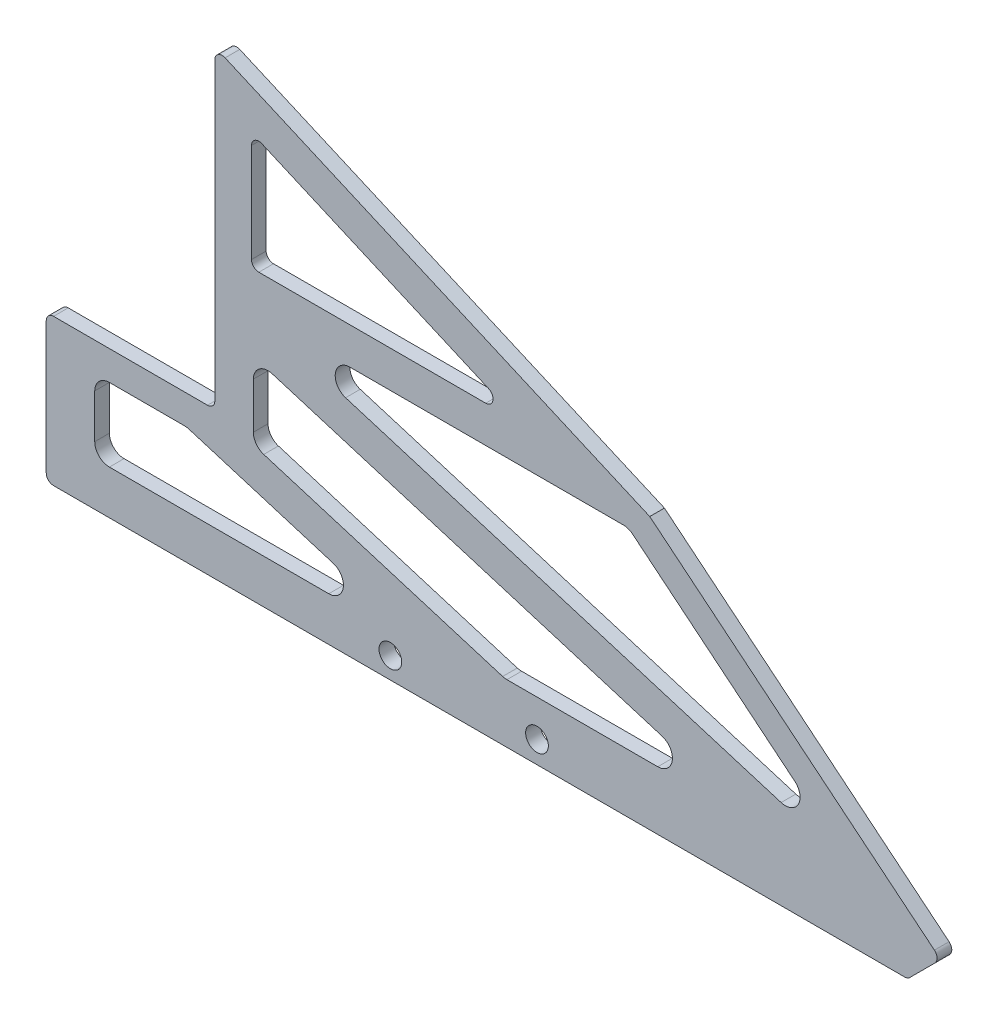
SolidWorks part; units mm, degrees
material "Thornel Mat VMA"
ref_plane "前视基准面" through (0, 0, 0) normal (0, 0, 1) x (1, 0, 0)
ref_plane "上视基准面" through (0, 0, 0) normal (0, 1, 0) x (1, 0, 0)
ref_plane "右视基准面" through (0, 0, 0) normal (1, 0, 0) x (0, 0, -1)
sketch "Sketch1" plane through (0, 0, 0) normal (0, 0, 1) x (1, 0, 0)
  line L0 (0.2811, 65) -> (0.2811, 127.8433)
  line L1 (0.2811, 65) -> (144.627, 65)
  line L2 (144.627, 65) -> (0.2811, 127.8433)
extrude "Boss-Extrude1" add sketch "Sketch1" along normal blind 2
sketch "Sketch2" plane through (0, 0, 0) normal (0, 0, -1) x (-1, 0, 0)
  line L0 (-59.6075, 102.0146) -> (-104.7872, 65)
  line L1 (-144.627, 65) -> (-0.2811, 127.8433) construction
  line L2 (-0.2811, 65) -> (-144.627, 65) construction
  line L3 (-104.7872, 65) -> (-144.627, 65)
  line L4 (-144.627, 65) -> (-59.6075, 102.0146)
extrude "Cut-Extrude1" cut sketch "Sketch2" against normal through all both and the other way through all
sketch "Sketch3" plane through (0, 0, 2) normal (0, 0, 1) x (1, 0, 0)
  circle A0 centre (24.2214, 67.8936) radius 1.55
  circle A1 centre (44.2214, 68) radius 1.55
  dimension "D1" = 3.1
extrude "Cut-Extrude2" cut sketch "Sketch3" against normal through all
chamfer "Chamfer1" distance 10 angle 45 1 edges at (104.7872, 65, 1) first distance on face at (52.5342, 65, 1)
sketch "Sketch4" plane through (0, 0, 0) normal (0, 0, -1) x (-1, 0, 0)
  line L1 (-0.2811, 65) -> (22.7189, 65)
  line L2 (-0.2811, 65) -> (-0.2811, 85)
  line L3 (-0.2811, 85) -> (22.7189, 85)
  line L4 (22.7189, 65) -> (22.7189, 85)
  dimension "D1" = 23
  dimension "D2" = 20
extrude "Boss-Extrude2" add sketch "Sketch4" against normal blind 2
sketch "Sketch5" plane through (0, 0, 2) normal (0, 0, 1) x (1, 0, 0)
  line L0 (5.2811, 120.2131) -> (42.0318, 104.2131)
  line L1 (42.0318, 104.2131) -> (5.2811, 104.2131)
  line L2 (5.2811, 104.2131) -> (5.2811, 120.2131)
  line L3 (59.6075, 102.0146) -> (0.2811, 127.8433) construction
  line L4 (0.2811, 127.8433) -> (0.2811, 85) construction
  line L5 (5.2811, 99.2131) -> (56.7152, 99.2131)
  line L6 (56.7152, 99.2131) -> (87.2015, 74.2365)
  line L7 (87.2015, 74.2365) -> (5.2811, 99.2131)
  line L8 (99.2905, 69.5033) -> (59.6075, 102.0146) construction
  line L9 (5.5336, 93.9089) -> (74.1125, 73)
  line L13 (5.5336, 83.4545) -> (39.823, 73)
  line L14 (39.823, 73) -> (74.1125, 73)
  line L15 (5.5336, 83.4545) -> (5.5336, 93.9089)
  line L16 (-16.1041, 81) -> (-3.5608, 81)
  line L17 (-3.5608, 81) -> (29.2381, 71)
  line L18 (29.2381, 71) -> (-16.1041, 71)
  line L19 (-16.1041, 71) -> (-16.1041, 81)
  line L20 (-22.7189, 85) -> (0.2811, 85) construction
  line L21 (-22.7189, 65) -> (94.7872, 65) construction
  dimension "D1" = 5
  dimension "D2" = 5
  dimension "D3" = 16
  dimension "D4" = 4
  dimension "D5" = 5
  dimension "D6" = 0
  dimension "D7" = 15
  dimension "D8" = 4
  dimension "D9" = 5
  dimension "D10" = 6
  dimension "D11" = 10
  dimension "D12" = 5
extrude "Cut-Extrude3" cut sketch "Sketch5" against normal blind 10
fillet "Fillet1" radius 1 9 edges at (42.0318, 104.2131, 1) (5.2811, 120.2131, 1) (5.2811, 104.2131, 1) (0.2811, 127.8433, 1) (94.7872, 65, 1) (99.2905, 69.5033, 1) (-22.7189, 65, 1) (-22.7189, 85, 1) (0.2811, 85, 1)
fillet "Fillet2" radius 2 11 edges at (-3.5608, 81, 1) (-16.1041, 81, 1) (-16.1041, 71, 1) (29.2381, 71, 1) (39.823, 73, 1) (5.5336, 83.4545, 1) (5.5336, 93.9089, 1) (74.1125, 73, 1) (87.2015, 74.2365, 1) (56.7152, 99.2131, 1) (5.2811, 99.2131, 1)
